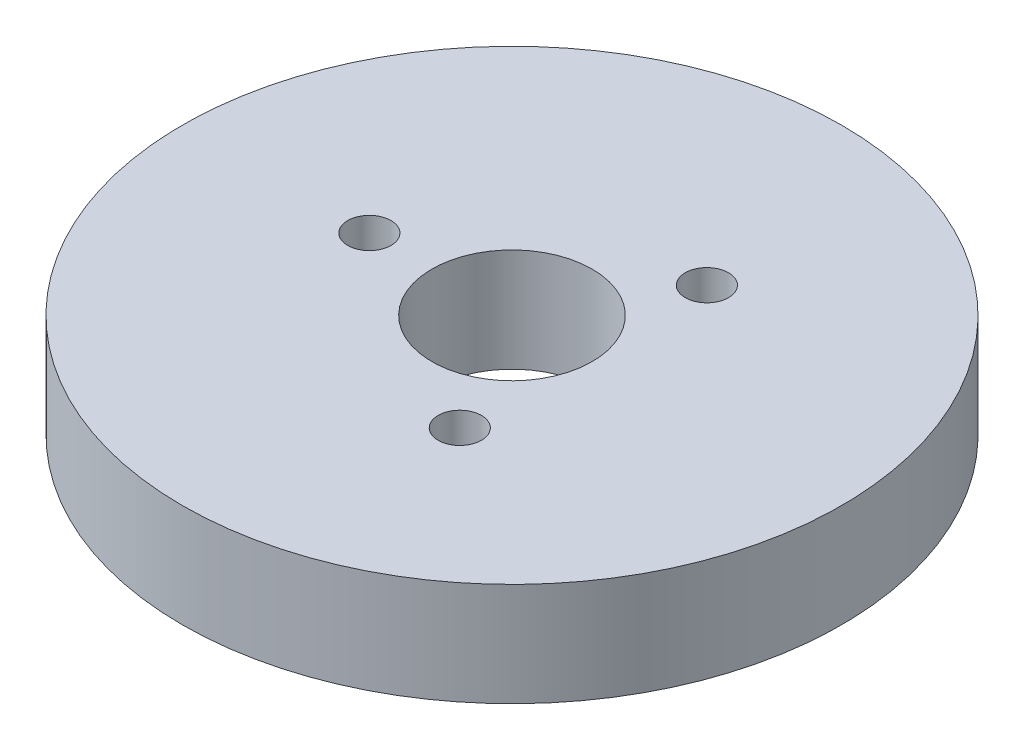
SolidWorks part; units mm, degrees
ref_plane "Front Plane" through (0, 0, 0) normal (0, 0, 1) x (1, 0, 0)
ref_plane "Top Plane" through (0, 0, 0) normal (0, 1, 0) x (1, 0, 0)
ref_plane "Right Plane" through (0, 0, 0) normal (1, 0, 0) x (0, 0, -1)
sketch "Sketch1" plane through (0, 0, 0) normal (0, 1, 0) x (1, 0, 0)
  circle A0 centre (0, 0) radius 92.5
  dimension "FLANGE_OD" = 185
extrude "Boss-Extrude1" add sketch "Sketch1" along normal blind 29
sketch "Sketch2" plane through (0, 0, 0) normal (0, 1, 0) x (1, 0, 0)
  circle A0 centre (0, 0) radius 22.5
  dimension "BORE_D" = 45
extrude "Cut-Extrude1" cut sketch "Sketch2" along normal through all
sketch "Sketch3" plane through (0, 29, 0) normal (0, 1, 0) x (1, 0, 0)
  circle A0 centre (0, 0) radius 40.0388 construction
  circle A1 centre (-40.0388, 0) radius 6.0709
  dimension "BOLT_D" = 12.1418
  dimension "BOLT_PCD" = 80.0776
extrude "Cut-Extrude2" cut sketch "Sketch3" against normal blind 19.544
pattern_circular "CirPattern1" count 3 over 360 about axis through (0, 0, 0) along (0, 1, 0) of "Cut-Extrude2"
